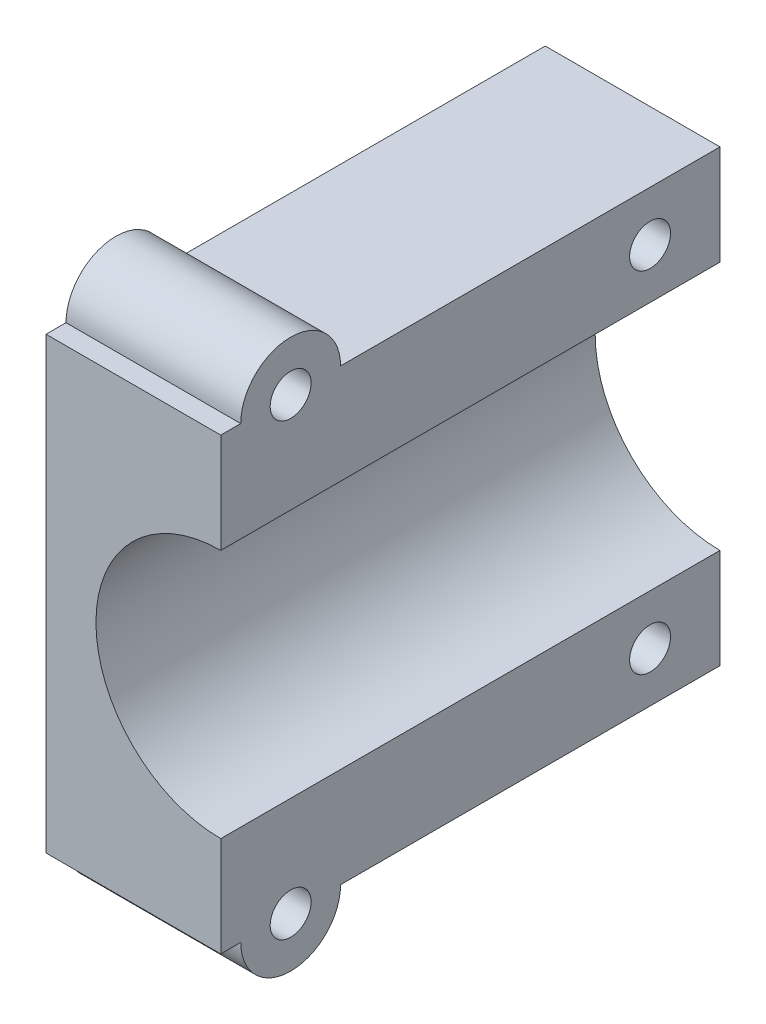
SolidWorks part; units mm, degrees
material "PLA"
ref_plane "Front Plane" through (0, 0, 0) normal (0, 0, 1) x (1, 0, 0)
ref_plane "Top Plane" through (0, 0, 0) normal (0, 1, 0) x (1, 0, 0)
ref_plane "Right Plane" through (0, 0, 0) normal (1, 0, 0) x (0, 0, -1)
sketch "Sketch1" plane through (0, 0, 0) normal (0, 0, 1) x (1, 0, 0)
  line L0 (-17.5, 22.5) -> (-17.5, 0)
  line L1 (55, 0) -> (-55, 0) construction
  line L2 (-17.5, 0) -> (17.5, 0)
  line L3 (17.5, 0) -> (17.5, 22.5)
  line L4 (-17.5, 22.5) -> (-12.5, 22.5)
  line L5 (17.5, 22.5) -> (12.5, 22.5)
  line L6 (0, -44.7868) -> (0, 44.7868) construction
  arc A0 (-12.5, 22.5) -> (12.5, 22.5) centre (0, 22.5) ccw
  dimension "D1" = 12.5
  dimension "D2" = 22.5
  dimension "D3" = 5
extrude "Boss-Extrude1" add sketch "Sketch1" along normal mid plane 50
sketch "Construct1" plane through (0, 0, 0) normal (0, 1, 0) x (1, 0, 0)
  line L0 (17.5, 0) -> (43.4808, -15) construction
  line L1 (-44.2539, 0) -> (44.2539, 0) construction
  line L2 (34.7051, -0.1998) -> (26.2756, -14.8002) construction
  line L3 (17.5, -25) -> (17.5, 25) construction
  point P6 (30.4904, -7.5)
  point P7 (30.4904, -7.5)
  dimension "D1" = 30
  dimension "D2" = 15
ref_plane "LegBuildPlane" through (26.1154, 0, 15.0777) normal (0.866, 0, 0.5) x (0.5, 0, -0.866)
sketch "Sketch5" plane through (26.1154, 0, 15.0777) normal (0.866, 0, 0.5) x (0.5, 0, -0.866)
  line L0 (-8.7, 22.5) -> (-3.75, 22.5)
  line L1 (21.25, 22.5) -> (26.2, 22.5)
  line L2 (17.1795, 0) -> (0.3205, 0) construction
  arc A0 (-3.75, 22.5) -> (21.25, 22.5) centre (8.75, 22.5) ccw
  arc A1 (-8.7, 22.5) -> (26.2, 22.5) centre (8.75, 22.5) ccw
  point P9 (8.75, 0)
  dimension "D1" = 17.45
  dimension "D2" = 12.5
  dimension "D3" = 22.5
  dimension "D4" = 0
extrude "Boss-Extrude2" add sketch "Sketch5" against normal up to surface and the other way blind 30 up to face at (17.5, 11.25, 0)
sketch "Sketch9" plane through (-17.5, 0, 0) normal (-1, 0, 0) x (0, 0, 1)
  line L2 (55, 0) -> (-55, 0) construction
  line L3 (-25, 22.5) -> (-25, 0) construction
  circle A0 centre (-18, 5) radius 2.05
  dimension "D1" = 4.1
  dimension "D2" = 5
  dimension "D3" = 7
extrude "Cut-Extrude3" cut sketch "Sketch9" against normal up to surface (35 mm away) up to face at (17.5, 12.0917, 0)
sketch "Construct2" plane through (0, 22.5, 0) normal (0, 1, 0) x (1, 0, 0)
  line L0 (20.0981, -15.9338) -> (32.5981, 5.7169) construction
  line L2 (50.2211, -33.3253) -> (17.5, -14.4338) construction
  line L3 (62.7211, -11.6747) -> (17.5, 14.4338) construction
  line L4 (17.5, 0) -> (26.3481, -5.1084) construction
  line L11 (-44.2539, 0) -> (44.2539, 0) construction
  dimension "D1" = 3
  dimension "D2" = 90
ref_plane "LegBuildPlane2" through (21.9731, 0, 12.6862) normal (0.866, 0, 0.5) x (0.5, 0, -0.866)
sketch "Sketch12" plane through (21.9731, 0, 12.6862) normal (0.866, 0, 0.5) x (0.5, 0, -0.866)
  line L0 (-3.75, 22.5) -> (21.25, 22.5)
  arc A0 (-3.75, 22.5) -> (21.25, 22.5) centre (8.75, 22.5) ccw
extrude "Boss-Extrude5" add sketch "Sketch12" against normal up to surface (17.4338 mm away) up to face at (17.5, 16.25, 0)
mirror "Mirror1" about plane through (17.5, 22.5, 25) normal (0, -1, 0) of "Boss-Extrude2", "Boss-Extrude1", "Cut-Extrude3", "Boss-Extrude5"
sketch "Sketch13" plane through (0, 0, 0) normal (0, 1, 0) x (1, 0, 0)
  line L0 (17.5, 0) -> (43.4808, -15) construction
  line L1 (47.7461, -37.6121) -> (65.1961, -7.3879) construction
  circle A0 centre (43.4808, -15) radius 1.55
  dimension "D2" = 3.1
  dimension "D1" = 15
extrude "Cut-Extrude4" cut sketch "Sketch13" along normal through all
sketch "Sketch16" plane through (0, 0, 0) normal (1, 0, 0) x (0, 0, -1)
  line L1 (25, 45) -> (-38, 45)
  line L2 (25, 45) -> (25, 0)
  line L3 (25, 0) -> (-38, 0)
  line L4 (-38, 45) -> (-38, 0)
  line L7 (55, 0) -> (-55, 0) construction
  line L8 (0, 44.2539) -> (0, -44.2539) construction
  dimension "D1" = 38
extrude "Cut-Extrude5" cut sketch "Sketch16" along normal up to surface (83.8953 mm away) up to face at (65.1961, 22.5, 7.3879)
sketch "Sketch17" plane through (-17.5, 0, 0) normal (-1, 0, 0) x (0, 0, 1)
  line L0 (55, 0) -> (-55, 0) construction
  line L1 (13, 0) -> (23, 0)
  arc A0 (13, 0) -> (23, 0) centre (18, 0) ccw
  circle A1 centre (-18, 5) radius 2.05 construction
  dimension "D2" = 5
  dimension "D1" = 36
extrude "Boss-Extrude6" add sketch "Sketch17" against normal blind 17.5
sketch "Sketch18" plane through (-17.5, 0, 0) normal (-1, 0, 0) x (0, 0, 1)
  circle A0 centre (18, 0) radius 2.05
  dimension "D1" = 4.1
extrude "Cut-Extrude6" cut sketch "Sketch18" against normal up to surface (17.5 mm away) up to face at (0, 5, -15.95)
ref_plane "HolePlane" through (0, 22.5, 0) normal (0, 1, 0) x (1, 0, 0)
mirror "Mirror2" about plane through (0, 22.5, 0) normal (0, 1, 0) of "Boss-Extrude6", "Cut-Extrude6"
equation "\"TubeDiam\"= 12.5"
equation "\"D1@Sketch1\"=\"TubeDiam\""
equation "\"D2@Sketch1\"=\"ClampHeight\""
equation "\"MountLength\"= 50"
equation "\"D1@Boss-Extrude1\"=\"MountLength\""
equation "\"MountHoleSize\"=3.1"
equation "\"LipWidth\"= 5"
equation "\"D3@Sketch1\"=\"LipWidth\""
equation "\"LegDiam\"= 12.5"
equation "\"LegThickness\"= \"TubeDiam\" + 4.95"
equation "\"D1@Sketch5\"=\"LegThickness\""
equation "\"D2@Sketch5\"=\"TubeDiam\""
equation "\"ClampHeight\"= \"TubeDiam\" + 10"
equation "\"D3@Sketch5\"=\"ClampHeight\""
equation "\"HubHoleDist\"=7"
equation "\"HubHoleSize\"=4.1"
equation "\"D2@Sketch13\"=\"MountHoleSize\""
equation "\"D1@Sketch9\"=\"HubHoleSize\""
equation "\"D3@Sketch9\"=\"HubHoleDist\""
equation "\"D1@Sketch17\"=\"MountLength\" - 2 * \"HubHoleDist\""
equation "\"D1@Boss-Extrude6\"=\"TubeDiam\"+5"
equation "\"D1@Sketch18\"=\"HubHoleSize\""
